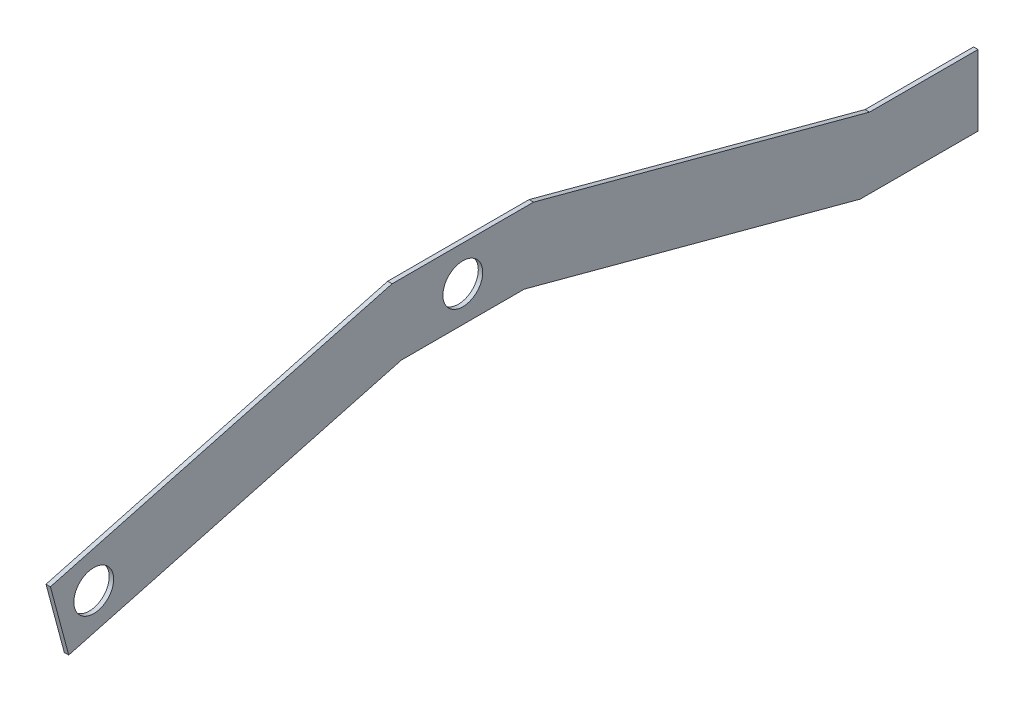
SolidWorks part; units mm, degrees
material "6063-O"
ref_plane "Front" through (0, 0, 0) normal (0, 0, 1) x (1, 0, 0)
ref_plane "Top" through (0, 0, 0) normal (0, 1, 0) x (1, 0, 0)
ref_plane "Right" through (0, 0, 0) normal (1, 0, 0) x (0, 0, -1)
sketch "Sketch1" plane through (0, 0, 0) normal (1, 0, 0) x (0, 0, -1)
  line L0 (-50.8, 25.4) -> (50.8, 25.4)
  line L3 (319.1634, -99.0998) -> (44.1121, -25.4)
  line L4 (44.1121, -25.4) -> (-44.1121, -25.4)
  line L5 (-44.1121, -25.4) -> (-282.9972, -89.4091)
  line L6 (-282.9972, -89.4091) -> (-296.1452, -40.34)
  line L7 (-296.1452, -40.34) -> (-50.8, 25.4)
  line L8 (0, 25.4) -> (0, -25.4) construction
  line L9 (-310.7646, -70.5533) -> (-48606.9507, -13011.4774) construction
  line L13 (601.9041, -58.3005) -> (-49398.0959, -58.3005) construction
  line L14 (-147.7421, -347.18) -> (49852.2579, -347.18) construction
  line L15 (369.9634, -60.1196) -> (369.9634, -337.7005)
  line L16 (369.9634, -337.7005) -> (319.1634, -337.7005)
  line L17 (319.1634, -337.7005) -> (319.1634, -99.0998)
  line L19 (50.8, 25.4) -> (369.9634, -60.1196)
  circle A0 centre (-265.0366, -58.3005) radius 14.2875
  circle A1 centre (0, 0) radius 14.2875
  point P10 (0, 0)
  point P16 (-289.5712, -64.8746)
  point P24 (344.5634, -337.7005)
  dimension "D8" = 28.575
  dimension "D1" = 50.8
  dimension "D2" = 50.8
  dimension "D3" = 609.6
  dimension "D4" = 279.4
  dimension "D5" = 254
  dimension "D6" = 165
  dimension "D7" = 101.6
  dimension "D9" = 25.4
  dimension "D10" = 50.8
  dimension "D11" = 347.18
  dimension "D13" = 50.8
extrude "Boss-Extrude1" add sketch "Sketch1" along normal blind 3.175
sketch "Sketch3" plane through (3.175, 0, 0) normal (1, 0, 0) x (0, 0, -1)
  line L0 (344.5634, -337.7005) -> (344.5634, -53.3137) construction
  line L1 (319.1634, -337.7005) -> (369.9634, -337.7005) construction
  line L2 (369.9634, -60.1196) -> (50.8, 25.4) construction
  circle A0 centre (344.5634, -312.3005) radius 12.7
  dimension "D1" = 25.4
  dimension "D2" = 25.4
extrude "Cut-Extrude2" cut sketch "Sketch3" against normal through all
sketch "Sketch5" plane through (3.175, 0, 0) normal (1, 0, 0) x (0, 0, -1)
  line L0 (369.9634, -337.7005) -> (369.9634, -60.1196) construction
  line L1 (319.1634, -337.7005) -> (369.9634, -337.7005)
  line L2 (319.1634, -337.7005) -> (319.1634, -90.0505)
  line L3 (319.1634, -90.0505) -> (369.9634, -90.0505)
  line L4 (369.9634, -337.7005) -> (369.9634, -90.0505)
  dimension "D1" = 247.65
extrude "Cut-Extrude4" cut sketch "Sketch5" against normal through all
sketch "Sketch6" plane through (3.175, 0, 0) normal (1, 0, 0) x (0, 0, -1)
  line L1 (369.9634, -90.0505) -> (242.9634, -90.0505)
  line L2 (369.9634, -90.0505) -> (369.9634, -115.4505)
  line L3 (369.9634, -115.4505) -> (242.9634, -115.4505)
  line L4 (242.9634, -90.0505) -> (242.9634, -115.4505)
  dimension "D1" = 25.4
  dimension "D2" = 127
extrude "Cut-Extrude5" cut sketch "Sketch6" against normal through all
sketch "Sketch7" plane through (3.175, 0, 0) normal (1, 0, 0) x (0, 0, -1)
  line L0 (292.0791, -39.2505) -> (369.9634, -39.2505)
  line L1 (369.9634, -60.1196) -> (50.8, 25.4) construction
  line L2 (369.9634, -39.2505) -> (369.9634, -60.1196)
  line L3 (369.9634, -90.0505) -> (285.3912, -90.0505) construction
  line L4 (292.0791, -39.2505) -> (369.9634, -60.1196)
  dimension "D1" = 50.8
extrude "Boss-Extrude2" add sketch "Sketch7" against normal blind 3.175
